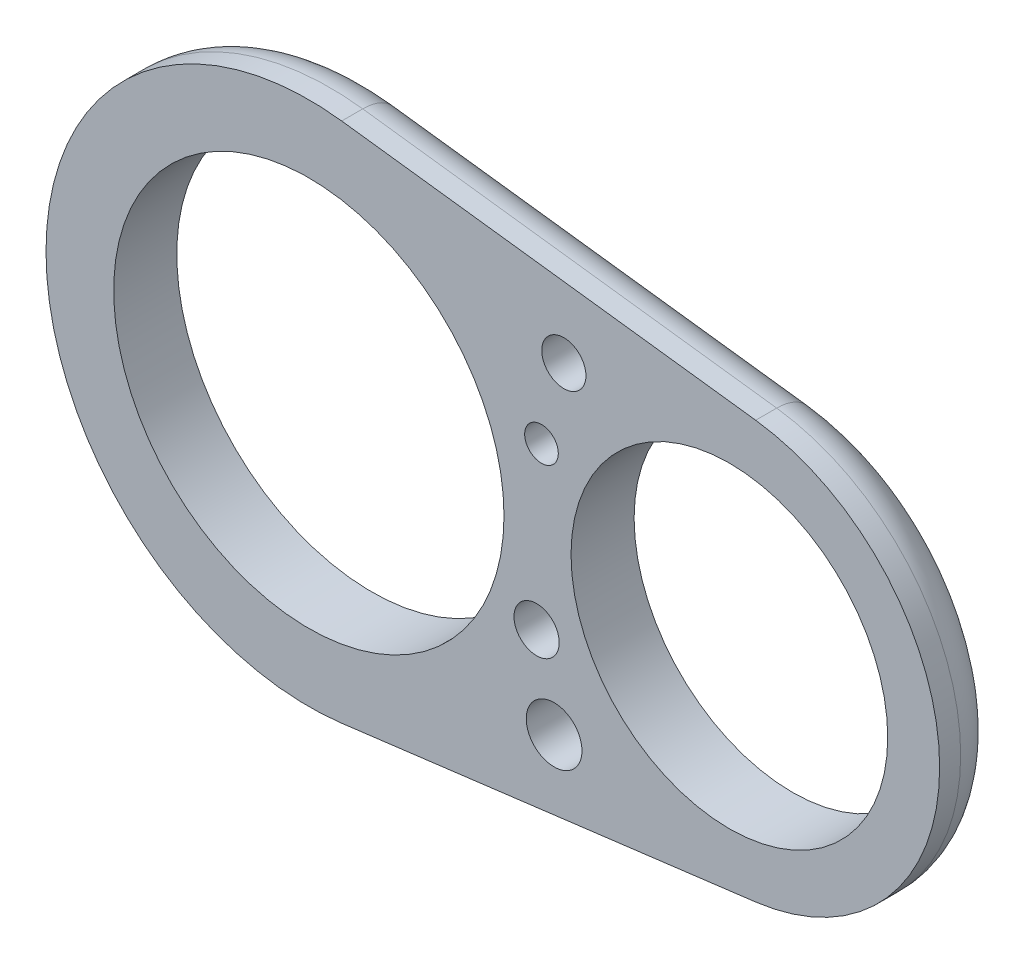
SolidWorks part; units mm, degrees
ref_plane "Front Plane" through (0, 0, 0) normal (0, 0, 1) x (1, 0, 0)
ref_plane "Top Plane" through (0, 0, 0) normal (0, 1, 0) x (1, 0, 0)
ref_plane "Right Plane" through (0, 0, 0) normal (1, 0, 0) x (0, 0, -1)
sketch "Sketch1" plane through (0, 0, 0) normal (0, 0, 1) x (1, 0, 0)
  line L0 (0, 0) -> (40, 0) construction
  line L4 (3.125, 24.8039) -> (42.5, 19.8431)
  line L5 (3.125, -24.8039) -> (42.5, -19.8431)
  line L6 (20, 0) -> (23.3266, -15.6504) construction
  line L7 (20, 0) -> (24.2533, 15.4243) construction
  circle A0 centre (0, 0) radius 18.5625
  circle A1 centre (40, 0) radius 15.0625
  arc A4 (3.125, 24.8039) -> (3.125, -24.8039) centre (0, 0) ccw
  arc A6 (42.5, -19.8431) -> (42.5, 19.8431) centre (40, 0) ccw
  arc A7 (24.9765, -1.0834) -> (24.9765, 1.0834) centre (0, 0) ccw
  circle A8 centre (23.3266, -15.6504) radius 2.65
  circle A9 centre (24.2533, 15.4243) radius 2.1
  circle A10 centre (22.1267, 7.7122) radius 1.6
  circle A11 centre (21.6633, -7.8252) radius 2.15
  dimension "D1" = 37.125
  dimension "D2" = 30.125
  dimension "D3" = 50
  dimension "D6" = 5.3
  dimension "D9" = 4.2
  dimension "D10" = 3.2
  dimension "D11" = 4.3
  dimension "D5" = 40
  dimension "D4" = 78
  dimension "D7" = 16
  dimension "D8" = 16
extrude "Boss-Extrude1" add sketch "Sketch1" along normal blind 6 contours L5 A6 L4 A4 A11 A10 A9 A8 A0 A1 region at (22.6892, 21.3451, 0)
fillet "Fillet1" radius 4 4 edges at (-25, 0, 0) (22.8125, -22.3235, 0) (60, 0, 0) (22.8125, 22.3235, 0)
equation "\"thighLength\"=185"
equation "\"legLength\"=200"
equation "\"m3Thru\"=3.2"
equation "\"m4Thru\"=4.3"
equation "\"m3Insert\"=4.2"
equation "\"m4Insert\"=5.3"
equation "\"shoulder5mm\"=5.1"
equation "\"6706out\"=37.125"
equation "\"6706in\"=30"
equation "\"6904out\"=30.125"
equation "\"6904in\"=17"
equation "\"D1@Sketch1\"=\"6706out\""
equation "\"D2@Sketch1\"=\"6904out\""
equation "\"D6@Sketch1\"=\"m4Insert\""
equation "\"D9@Sketch1\"=\"m3Insert\""
equation "\"D10@Sketch1\"=\"m3Thru\" "
equation "\"D11@Sketch1\"=\"m4Thru\""
